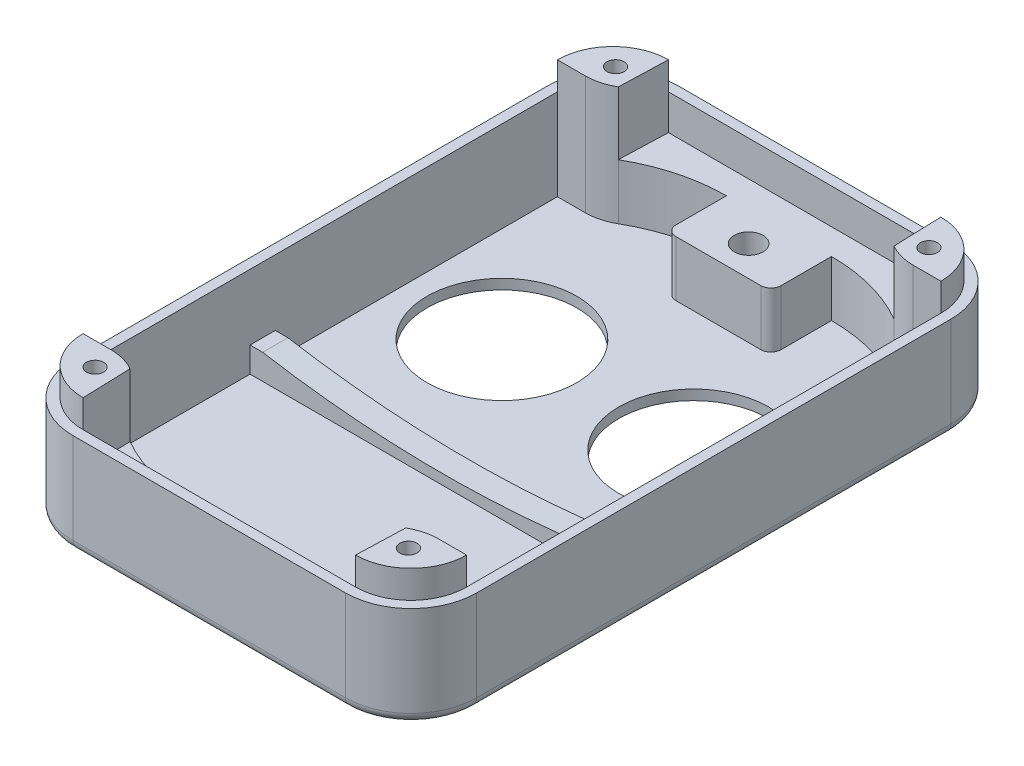
SolidWorks part; units mm, degrees
ref_plane "Alzado" through (0, 0, 0) normal (0, 0, 1) x (1, 0, 0)
ref_plane "Planta" through (0, 0, 0) normal (0, 1, 0) x (1, 0, 0)
ref_plane "Vista lateral" through (0, 0, 0) normal (1, 0, 0) x (0, 0, -1)
sketch "Croquis1" plane through (0, 0, 0) normal (0, 1, 0) x (1, 0, 0)
  line L0 (0, -55.2281) -> (0, 64.3245) construction
  line L1 (-27, 60) -> (27, 60)
  line L2 (-27, -60) -> (27, -60)
  line L3 (40, 47) -> (40, -47)
  line L5 (-40, 47) -> (-40, -47)
  line L6 (40, 47) -> (-40, -47) construction
  line L7 (40, -47) -> (-40, 47) construction
  arc A0 (27, 60) -> (40, 47) centre (27, 47) cw
  arc A1 (-27, 60) -> (-40, 47) centre (-27, 47) ccw
  arc A2 (-40, -47) -> (-27, -60) centre (-27, -47) ccw
  arc A3 (27, -60) -> (40, -47) centre (27, -47) ccw
  point P1 (0, 0)
  point P17 (0, 60)
  dimension "D2" = 80
  dimension "D3" = 13
  dimension "D1" = 120
extrude "Saliente-Extruir1" add sketch "Croquis1" along normal blind 20
shell "Vaciado1" thickness 2 removed face at (0, 20, 0)
sketch "Croquis2" plane through (0, 2, 0) normal (0, 1, 0) x (1, 0, 0)
  line L0 (0, 0) -> (0, -20.3372) construction
  line L1 (10.415, -33.255) -> (-10.415, -33.255) construction
  line L3 (10.415, -11.41) -> (10.415, -55.1) construction
  line L4 (10.415, -55.1) -> (-10.415, -55.1) construction
  line L5 (-10.415, -11.41) -> (-10.415, -55.1) construction
  line L8 (-27, -58) -> (27, -58) construction
  line L9 (0, -47) -> (-10.415, -47) construction
  line L10 (-27, -58) -> (27, -58)
  line L11 (0, -47) -> (10.415, -47) construction
  line L16 (-38, 0) -> (38, 0) construction
  line L17 (-38, 47) -> (-38, -47) construction
  line L18 (38, -47) -> (38, 47) construction
  line L19 (-10.415, 47) -> (-32.4711, 47) construction
  line L20 (10.415, 47) -> (32.4711, 47) construction
  line L21 (0, 47) -> (10.415, 47) construction
  line L22 (-10.415, -52.9) -> (10.415, -52.9)
  line L23 (-32.4711, -47) -> (-38, -47)
  line L24 (32.4711, -47) -> (38, -47)
  line L25 (10.415, -47) -> (32.4711, -47) construction
  line L26 (-10.415, -47) -> (-32.4711, -47) construction
  line L27 (0, 47) -> (-10.415, 47) construction
  line L29 (32.4711, 47) -> (38, 47)
  line L30 (-32.4711, 47) -> (-38, 47)
  line L31 (-10.415, 52.9) -> (10.415, 52.9)
  line L32 (-27, 58) -> (27, 58)
  arc A4 (-38, -47) -> (-27, -58) centre (-27, -47) ccw construction
  arc A5 (-38, -47) -> (-27, -58) centre (-27, -47) ccw
  arc A6 (27, -58) -> (38, -47) centre (27, -47) ccw construction
  arc A7 (-38, -47) -> (-27, -58) centre (-27, -47) ccw construction
  arc A8 (27, -58) -> (38, -47) centre (27, -47) ccw
  arc A9 (-10.415, 52.9) -> (-27.319, 48.3782) centre (-10.415, 19.0428) ccw
  arc A10 (-27.319, 48.3782) -> (-32.4711, 47) centre (-32.4711, 57.3191) cw
  arc A11 (10.415, -52.9) -> (27.319, -48.3782) centre (10.415, -19.0428) ccw
  arc A12 (27.319, -48.3782) -> (32.4711, -47) centre (32.4711, -57.3191) cw
  arc A13 (-27.319, -48.3782) -> (-32.4711, -47) centre (-32.4711, -57.3191) ccw
  arc A14 (-10.415, -52.9) -> (-27.319, -48.3782) centre (-10.415, -19.0428) cw
  arc A15 (27.319, 48.3782) -> (32.4711, 47) centre (32.4711, 57.3191) ccw
  arc A16 (10.415, 52.9) -> (27.319, 48.3782) centre (10.415, 19.0428) cw
  arc A17 (27, 58) -> (38, 47) centre (27, 47) cw
  arc A18 (-38, 47) -> (-27, 58) centre (-27, 47) cw
  point P1 (0, 0)
  point P2 (0, -55.1)
  point P11 (0, -33.255)
  point P86 (0, 55.1)
  dimension "D8" = 33.8572
  dimension "D9" = 10.3191
  dimension "D1" = 43.69
  dimension "D2" = 20.83
  dimension "D6" = 2.9
  dimension "D7" = 5.1
extrude "Saliente-Extruir2" add sketch "Croquis2" along normal blind 11
sketch "Croquis3" plane through (0, 13, 0) normal (0, 1, 0) x (1, 0, 0)
  line L0 (-27, 58) -> (-27.319, 48.3782) construction
  line L1 (-27.319, 48.3782) -> (-34.7782, 54.7782) construction
  line L2 (0, 0) -> (0, 36.3825) construction
  line L3 (0, 0) -> (56.4797, 0) construction
  arc A0 (-27, 58) -> (-38, 47) centre (-27, 47) ccw construction
  arc A1 (-34.7782, 54.7782) -> (-27, 58) centre (-27.7097, 48.7134) cw construction
  circle A2 centre (-31.0486, 51.5782) radius 1.7
  circle A3 centre (31.0486, 51.5782) radius 1.7
  circle A4 centre (31.0486, -51.5782) radius 1.7
  circle A5 centre (-31.0486, -51.5782) radius 1.7
  point P9 (-34.7782, 54.7782)
  point P10 (-31.0486, 51.5782)
  dimension "D1" = 3.4
sketch "Croquis4" plane through (0, 13, 0) normal (0, 1, 0) x (1, 0, 0)
  line L0 (-38, 47) -> (-32.4711, 47)
  line L1 (-27, 58) -> (-27.319, 48.3782)
  arc A1 (-10.415, 52.9) -> (-27.319, 48.3782) centre (-10.415, 19.0428) ccw construction
  arc A2 (-27, 58) -> (-38, 47) centre (-27, 47) ccw
  arc A3 (-27, 58) -> (-38, 47) centre (-27, 47) ccw construction
  arc A5 (-10.415, 52.9) -> (-27.319, 48.3782) centre (-10.415, 19.0428) ccw construction
  arc A6 (-27.319, 48.3782) -> (-32.4711, 47) centre (-32.4711, 57.3191) cw
  arc A8 (-32.4711, 47) -> (-27.319, 48.3782) centre (-32.4711, 57.3191) ccw construction
  point P9 (-23.3693, 50.3237)
extrude "Saliente-Extruir3" add sketch "Croquis4" along normal blind 12.5
mirror "Simetría1" about plane through (0, 0, 0) normal (1, 0, 0) of "Saliente-Extruir3"
mirror "Simetría2" about plane through (0, 0, 0) normal (0, 0, 1) of "Simetría1", "Saliente-Extruir3"
sketch "Croquis5" plane through (0, 2, 0) normal (0, 1, 0) x (1, 0, 0)
  line L1 (-38, 32) -> (38, 32) construction
  line L2 (-38, 32) -> (-38, 2) construction
  line L3 (-38, 2) -> (38, 2) construction
  line L4 (38, 32) -> (38, 2) construction
  line L6 (0, 34) -> (0, 0) construction
  line L7 (-38, 17) -> (38, 17) construction
  line L8 (-38, 32) -> (0, 2) construction
  line L9 (0, 32) -> (-38, 2) construction
  line L12 (-38, 47) -> (-38, -47) construction
  circle A0 centre (-19, 17) radius 14.85
  circle A1 centre (19, 17) radius 14.85
  point P14 (0, 2)
  point P16 (0, 17)
  point P19 (-19, 17)
  dimension "D1" = 29.7
  dimension "D2" = 2
  dimension "D3" = 30
extrude "Cortar-Extruir1" cut sketch "Croquis5" against normal up to next
extrude "Cortar-Extruir2" cut sketch "Croquis3" against normal through all and the other way through all
fillet "Redondeo1" radius 2 8 edges at (0, 0, 60) (36.1924, 0, 56.1924) (40, 0, 0) (36.1924, 0, -56.1924) (0, 0, -60) (-36.1924, 0, -56.1924) (-40, 0, 0) (-36.1924, 0, 56.1924)
sketch "Croquis6" plane through (0, 2, 0) normal (0, 1, 0) x (1, 0, 0)
  line L0 (-38, 47) -> (-38, -47) construction
  line L1 (38, -8.91) -> (-38, -8.91)
  line L2 (38, -8.91) -> (38, -13.91)
  line L3 (38, -13.91) -> (-38, -13.91)
  line L4 (-38, -8.91) -> (-38, -13.91)
  line L5 (38, -8.91) -> (-38, -13.91) construction
  line L6 (38, -13.91) -> (-38, -8.91) construction
  line L7 (0, 0) -> (0, -20.9676) construction
  point P0 (0, -11.41)
  dimension "D1" = 5
  dimension "D2" = 11.41
extrude "Saliente-Extruir4" add sketch "Croquis6" along normal blind 5
sketch "Croquis7" plane through (0, 0, 13.91) normal (0, 0, 1) x (1, 0, 0)
  line L0 (-38, 7) -> (38, 7) construction
  line L1 (0, 7) -> (0, 0) construction
  line L2 (35.5, 7) -> (38, 7) construction
  line L3 (38, 7) -> (38, 2) construction
  line L4 (38, 7) -> (38, 2) construction
  line L5 (38, 2) -> (-38, 2) construction
  line L6 (-38, 2) -> (-38, 7) construction
  line L7 (-38, 7) -> (-35.5, 7) construction
  line L8 (-35.5, 7) -> (35.5, 7)
  arc A0 (-35.5, 7) -> (35.5, 7) centre (0, 215.5417) ccw
  point P8 (0, 4)
  dimension "D1" = 2.5
  dimension "D2" = 3
  dimension "D3" = 2.5
extrude "Cortar-Extruir3" cut sketch "Croquis7" against normal blind 5
sketch "Croquis8" plane through (0, 2, 0) normal (0, 1, 0) x (1, 0, 0)
  line L0 (0, 0) -> (0, 47.1931) construction
  line L1 (-10.415, 52.9) -> (10.415, 52.9) construction
  line L2 (10.415, 40.9) -> (-10.415, 40.9)
  line L3 (10.415, 40.9) -> (10.415, 52.9)
  line L4 (10.415, 52.9) -> (-10.415, 52.9)
  line L5 (-10.415, 40.9) -> (-10.415, 52.9)
  line L6 (10.415, 40.9) -> (-10.415, 52.9) construction
  line L7 (10.415, 52.9) -> (-10.415, 40.9) construction
  point P1 (0, 46.9)
  dimension "D1" = 12
extrude "Saliente-Extruir5" add sketch "Croquis8" along normal up to surface (11 mm away) up to face at (0, 13, -53.463)
fillet "Redondeo2" radius 2 2 edges at (10.415, 7.5, -40.9) (-10.415, 7.5, -40.9)
sketch "Croquis9" plane through (0, 13, 0) normal (0, 1, 0) x (1, 0, 0)
  line L0 (8.415, 40.9) -> (-8.415, 40.9) construction
  line L1 (-10.415, 52.9) -> (-10.415, 40.9) construction
  line L2 (10.415, 52.9) -> (10.415, 40.9) construction
  line L3 (-10.415, 40.9) -> (10.415, 40.9) construction
  line L4 (-10.415, 42.9) -> (-10.415, 52.9) construction
  line L5 (-10.415, 52.9) -> (10.415, 40.9) construction
  line L6 (-10.415, 40.9) -> (10.415, 52.9) construction
  line L9 (-10.415, 52.9) -> (10.415, 52.9) construction
  circle A0 centre (0, 46.9) radius 2.6
  point P0 (0, 46.9)
  dimension "D3" = 5.2
  dimension "D1" = 12
  dimension "D2" = 20.83
sketch "Croquis10" plane through (0, 13, 0) normal (0, 1, 0) x (1, 0, 0)
  circle A0 centre (0, 46.9) radius 2.85
  dimension "D1" = 5.7
extrude "Cortar-Extruir4" cut sketch "Croquis10" against normal blind 6
extrude "Cortar-Extruir5" cut sketch "Croquis9" against normal through all
sketch "Croquis11" plane through (0, 0, 0) normal (0, -1, 0) x (1, 0, 0)
  line L0 (0, -51.5782) -> (0, 51.5782) construction
  line L1 (-31.0486, -51.5782) -> (31.0486, -51.5782) construction
  line L2 (-31.0486, -51.5782) -> (-31.0486, 51.5782) construction
  line L3 (-31.0486, 51.5782) -> (31.0486, 51.5782) construction
  line L4 (31.0486, -51.5782) -> (31.0486, 51.5782) construction
  line L5 (-31.0486, 0) -> (0, 0) construction
  line L6 (0, 0) -> (31.0486, 0) construction
  circle A0 centre (-31.0486, -51.5782) radius 2.9
  circle A1 centre (31.0486, -51.5782) radius 2.9
  circle A2 centre (-31.0486, 51.5782) radius 2.9
  circle A3 centre (31.0486, 51.5782) radius 2.9
  dimension "D1" = 5.8
extrude "Cortar-Extruir6" cut sketch "Croquis11" against normal blind 3
